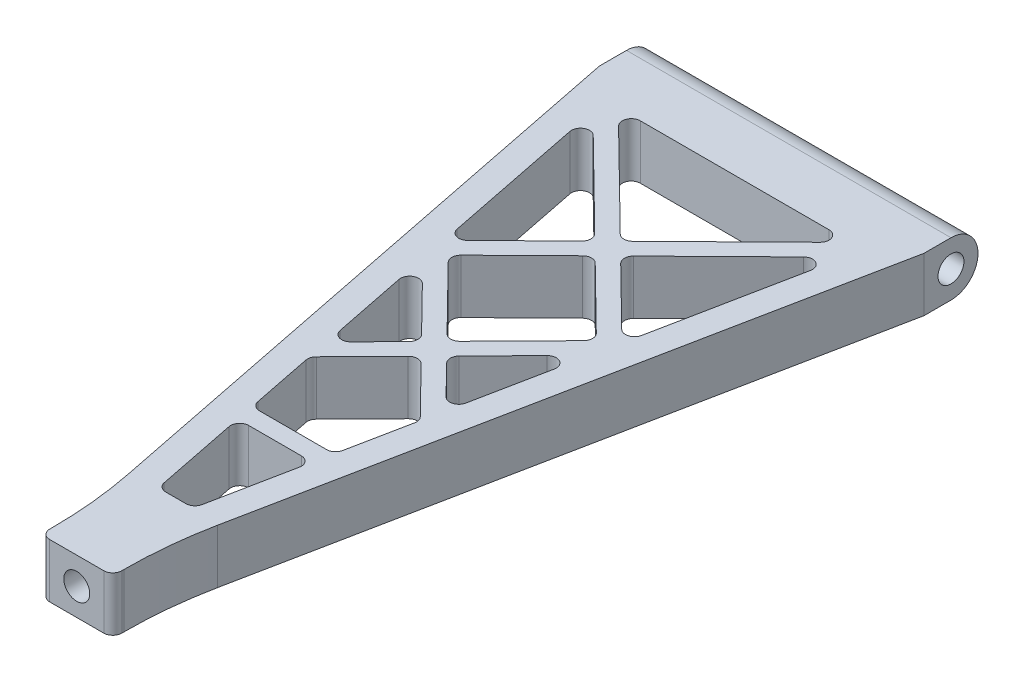
SolidWorks part; units mm, degrees
ref_plane "Front Plane" through (0, 0, 0) normal (0, 0, 1) x (1, 0, 0)
ref_plane "Top Plane" through (0, 0, 0) normal (0, 1, 0) x (1, 0, 0)
ref_plane "Right Plane" through (0, 0, 0) normal (1, 0, 0) x (0, 0, -1)
sketch "Sketch1" plane through (0, 0, 0) normal (0, 1, 0) x (1, 0, 0)
  line L0 (0, 0) -> (0, -120.65) construction
  line L1 (-28.575, 0) -> (28.575, 0) construction
  line L2 (-28.575, 4.7625) -> (-28.575, -4.7625)
  line L3 (28.575, 4.7625) -> (28.575, -4.7625)
  line L4 (-6.35, -120.65) -> (6.35, -120.65) construction
  line L5 (-6.35, -115.8875) -> (-6.35, -125.4125)
  line L6 (6.35, -115.8875) -> (6.35, -125.4125)
  line L7 (-28.575, -4.7625) -> (-6.35, -115.8875)
  line L8 (28.575, -4.7625) -> (6.35, -115.8875)
  line L9 (-6.35, -125.4125) -> (6.35, -125.4125)
  line L13 (-28.575, 4.7625) -> (28.575, 4.7625)
  line L14 (-28.575, -4.7625) -> (28.575, -4.7625)
  line L15 (-6.35, -115.8875) -> (6.35, -115.8875)
  line L16 (-19.05, 4.7625) -> (-19.05, -4.7625)
  line L17 (-19.05, -4.7625) -> (19.05, -4.7625)
  line L18 (19.05, -4.7625) -> (19.05, 4.7625)
  point P6 (0, 0)
  point P9 (-28.575, 0)
  point P11 (28.575, 0)
  point P16 (0, -120.65)
  point P18 (-6.35, -120.65)
  point P21 (6.35, -120.65)
  dimension "D1" = 9.525
  dimension "D2" = 57.15
  dimension "D3" = 9.525
  dimension "D4" = 12.7
  dimension "D5" = 120.65
  dimension "D8" = 9.525
  dimension "D9" = 9.525
extrude "Boss-Extrude1" add sketch "Sketch1" along normal blind 9.525 contours L16 L13 L2 L14 | L18 L14 L3 L13 | L7 L15 L8 L14 | L15 L5 L9 | L9 | L15 L9 L6 | L6 L9 L5 L7 L2 L13 L3 L8 region at (-23.8125, 0, 0) region at (0, 0, 48.539) region at (0, 0, 120.65) region at (23.8125, 0, 0)
sketch "Sketch6" plane through (-28.575, 0, 0) normal (-1, 0, 0) x (0, 0, 1)
  line L0 (-4.7625, 9.525) -> (-4.7625, 0) construction
  circle A0 centre (0, 4.7625) radius 2.286
  point P2 (-4.7625, 4.7625)
  point P3 (0, 0)
  point P6 (0, 0)
  point P8 (0, 0)
  dimension "D1" = 4.572
extrude "Cut-Extrude2" cut sketch "Sketch6" against normal through all both and the other way through all
sketch "Sketch7" plane through (0, 0, 125.4125) normal (0, 0, 1) x (1, 0, 0)
  line L0 (-6.35, 9.525) -> (-6.35, 0) construction
  circle A0 centre (0, 4.7625) radius 2.286
  point P2 (0, 0)
  point P4 (-6.35, 4.7625)
  dimension "D1" = 4.572
extrude "Cut-Extrude3" cut sketch "Sketch7" against normal blind 12.7
fillet "Fillet3" radius 76.2 2 edges at (6.35, 4.7625, 115.8875) (-6.35, 4.7625, 115.8875)
fillet "Fillet4" radius 1.5875 2 edges at (6.35, 4.7625, 125.4125) (-6.35, 4.7625, 125.4125)
fillet "Fillet5" radius 4.7625 2 edges at (0, 0, -4.7625) (0, 9.525, -4.7625)
sketch "Sketch8" plane through (0, 9.525, 0) normal (0, 1, 0) x (1, 0, 0)
  line L0 (-28.575, -4.7625) -> (28.575, -4.7625)
  line L1 (-7.1079, -112.7125) -> (7.1079, -112.7125)
  line L2 (-23.905, -3.8285) -> (-3.1597, -107.5547)
  line L3 (-1.6353, -120.65) -> (-1.6353, -120.65)
  line L4 (-1.6353, -120.65) -> (1.6353, -120.65)
  line L5 (1.6353, -120.65) -> (1.6353, -120.65)
  line L6 (3.1597, -107.5547) -> (23.905, -3.8285)
  line L7 (-28.575, -9.525) -> (28.575, -9.525)
  line L8 (28.575, -4.7625) -> (28.575, 0)
  line L9 (28.575, 0) -> (-28.575, 0)
  line L10 (-28.575, 0) -> (-28.575, -4.7625)
  line L11 (-28.575, -4.7625) -> (-7.8298, -108.4887)
  line L12 (-6.35, -123.4328) -> (-6.35, -123.825)
  line L13 (-4.7625, -125.4125) -> (4.7625, -125.4125)
  line L14 (6.35, -123.825) -> (6.35, -123.4328)
  line L15 (7.8298, -108.4887) -> (28.575, -4.7625)
  line L16 (28.575, -4.7625) -> (28.575, 0)
  line L17 (28.575, 0) -> (-28.575, 0)
  line L18 (-28.575, 0) -> (-28.575, -4.7625)
  line L19 (-28.575, -4.7625) -> (-7.8298, -108.4887)
  line L20 (-6.35, -123.4328) -> (-6.35, -123.825)
  line L21 (-4.7625, -125.4125) -> (4.7625, -125.4125)
  line L22 (6.35, -123.825) -> (6.35, -123.4328)
  line L23 (7.8298, -108.4887) -> (28.575, -4.7625)
  line L24 (-7.1079, -107.95) -> (7.1079, -107.95)
  line L25 (-22.7657, -9.525) -> (15.2908, -46.8996)
  line L26 (15.2908, -46.8996) -> (-10.1166, -72.7705)
  line L27 (22.7657, -9.525) -> (-15.2908, -46.8996)
  line L28 (-15.2908, -46.8996) -> (10.1166, -72.7705)
  line L29 (-6.8907, -88.9) -> (6.8907, -88.9)
  line L30 (-23.878, -10.6576) -> (13.0458, -46.9199)
  line L31 (13.0458, -46.9199) -> (-11.2492, -71.6581)
  line L32 (21.6533, -8.3924) -> (-17.5357, -46.8793)
  line L33 (-17.5357, -46.8793) -> (9.7401, -74.6528)
  line L34 (-6.8907, -90.4875) -> (6.8907, -90.4875)
  line L35 (-21.6533, -8.3924) -> (17.5357, -46.8793)
  line L36 (17.5357, -46.8793) -> (-9.7401, -74.6528)
  line L37 (23.878, -10.6576) -> (-13.0458, -46.9199)
  line L38 (-13.0458, -46.9199) -> (11.2492, -71.6581)
  line L39 (-7.2082, -87.3125) -> (7.2082, -87.3125)
  line L40 (-6.8907, -87.3125) -> (6.8907, -87.3125) construction
  line L41 (17.5357, -46.8793) -> (-8.984, -73.8828) construction
  line L42 (-17.5357, -46.8793) -> (8.984, -73.8828) construction
  arc A0 (-1.6353, -120.65) -> (-3.1597, -107.5547) centre (-82.55, -123.4328) ccw
  arc A1 (-1.6353, -120.65) -> (-1.6353, -120.65) centre (-1.6353, -120.65) ccw
  arc A2 (1.6353, -120.65) -> (1.6353, -120.65) centre (1.6353, -120.65) ccw
  arc A3 (3.1597, -107.5547) -> (1.6353, -120.65) centre (82.55, -123.4328) ccw
  arc A4 (-6.35, -123.4328) -> (-7.8298, -108.4887) centre (-82.55, -123.4328) ccw
  arc A5 (-6.35, -123.825) -> (-4.7625, -125.4125) centre (-4.7625, -123.825) ccw
  arc A6 (4.7625, -125.4125) -> (6.35, -123.825) centre (4.7625, -123.825) ccw
  arc A7 (7.8298, -108.4887) -> (6.35, -123.4328) centre (82.55, -123.4328) ccw
  arc A8 (-6.35, -123.4328) -> (-7.8298, -108.4887) centre (-82.55, -123.4328) ccw
  arc A9 (-6.35, -123.825) -> (-4.7625, -125.4125) centre (-4.7625, -123.825) ccw
  arc A10 (4.7625, -125.4125) -> (6.35, -123.825) centre (4.7625, -123.825) ccw
  arc A11 (7.8298, -108.4887) -> (6.35, -123.4328) centre (82.55, -123.4328) ccw
  dimension "D2" = 12.7
  dimension "D6" = 53.34
  dimension "D7" = 19.05
  dimension "D1" = 0
  dimension "D3" = 4.7625
  dimension "D4" = 4.7625
  dimension "D5" = 4.7625
  dimension "D8" = 1.5875
  dimension "D9" = 1.5875
extrude "Cut-Extrude4" cut sketch "Sketch8" against normal through all both and the other way through all contours A3 L6 L34 L2 A0 L24 | L2 L39 L6 L33 L36 | L36 L38 L6 | L33 L2 L31 | L37 L38 L31 L30 | L32 L30 L2 | L7 L35 L32 | L6 L37 L35 region at (-13.3801, 9.525, 29.7389) region at (0, 9.525, 16.2359) region at (13.3801, 9.525, 29.7389) region at (0, 9.525, 98.1659) region at (-9.1466, 9.525, 61.034) region at (0, 9.525, 47.0772) region at (9.1466, 9.525, 61.034) region at (0, 9.525, 77.7738)
fillet "Fillet6" radius 1.5875 28 edges at (3.0817, 4.7625, 107.95) (-3.0817, 4.7625, 107.95) (-6.5732, 4.7625, 90.4875) (6.5732, 4.7625, 90.4875) (-15.6627, 4.7625, 45.0399) (-22.2119, 4.7625, 12.2939) (-2.2656, 4.7625, 31.8828) (2.2656, 4.7625, 31.8828) (22.2119, 4.7625, 12.2939) (15.6627, 4.7625, 45.0399) (10.4931, 4.7625, 70.8882) (2.225, 4.7625, 62.4693) (14.7218, 4.7625, 49.7446) (9.7401, 4.7625, 74.6528) (7.2082, 4.7625, 87.3125) (-7.2082, 4.7625, 87.3125) (-9.7401, 4.7625, 74.6528) (13.0458, 4.7625, 46.9199) (0, 4.7625, 60.2037) (-13.0458, 4.7625, 46.9199) (0, 4.7625, 34.1079) (-2.225, 4.7625, 62.4693) (-10.4931, 4.7625, 70.8882) (-14.7218, 4.7625, 49.7446) (20.5, 4.7625, 9.525) (0, 4.7625, 29.6578) (-20.5, 4.7625, 9.525) (0, 4.7625, 64.735)
